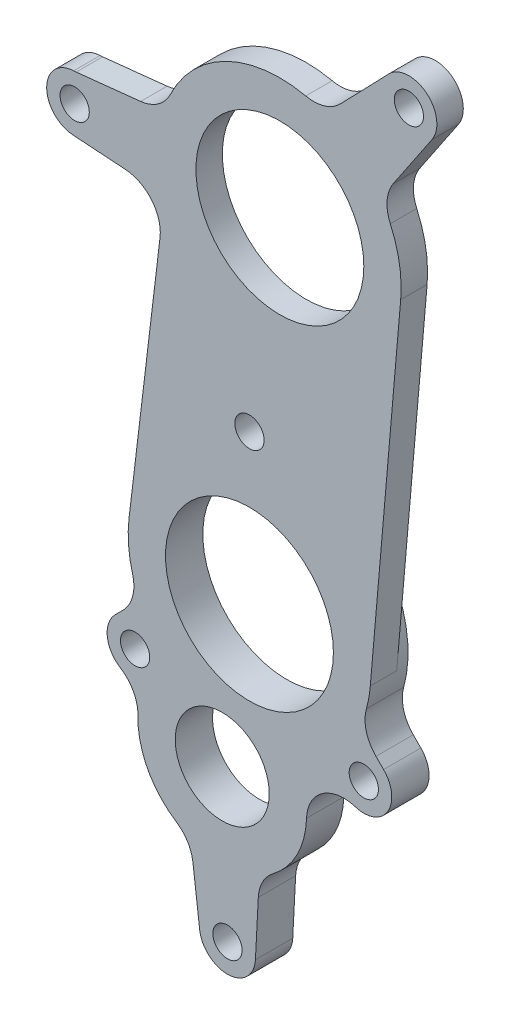
SolidWorks part; units mm, degrees
material "6061-T6 (SS)"
ref_plane "Front Plane" through (0, 0, 0) normal (0, 0, 1) x (1, 0, 0)
ref_plane "Top Plane" through (0, 0, 0) normal (0, 1, 0) x (1, 0, 0)
ref_plane "Right Plane" through (0, 0, 0) normal (1, 0, 0) x (0, 0, -1)
sketch "Sketch1" plane through (0, 0, 0) normal (0, 0, 1) x (1, 0, 0)
  line L0 (0, 0) -> (0, 25.4) construction
  line L1 (0, 0) -> (19.4575, -16.3268) construction
  line L2 (0, 0) -> (-19.4575, -16.3268) construction
  line L3 (-4.7444, 25.8151) -> (-5.2569, 19.9567)
  line L4 (4.7444, 25.8151) -> (5.2569, 19.9567)
  line L5 (22.8251, -12.9592) -> (18.6668, -8.8009)
  line L6 (16.7259, -20.228) -> (11.9087, -16.855)
  line L7 (-16.7259, -20.228) -> (-11.9087, -16.855)
  line L8 (-18.6668, -8.8009) -> (-22.8251, -12.9592)
  circle A0 centre (19.4575, -16.3268) radius 4.7625
  circle A1 centre (0, 25.4) radius 4.7625
  circle A2 centre (-19.4575, -16.3268) radius 4.7625
  circle A3 centre (19.4575, -16.3268) radius 2.4892
  circle A4 centre (-19.4575, -16.3268) radius 2.4892
  circle A5 centre (0, 25.4) radius 2.4892
  circle A6 centre (0, 0) radius 14.2875
  circle A7 centre (0, 0) radius 20.6375
  dimension "D1" = 9.525
  dimension "D4" = 4.9784
  dimension "D13" = 6.35
  dimension "D14" = 28.575
  dimension "D2" = 25.4
  dimension "D5" = 130
  dimension "D6" = 130
  dimension "D7" = 5
  dimension "D8" = 5
  dimension "D9" = 5
  dimension "D10" = 5
  dimension "D11" = 5
  dimension "D12" = 5
extrude "Boss-Extrude1" add sketch "Sketch1" along normal mid plane 6.35 contours A7 A6 | A7 L4 A1 L3 | A7 L6 A0 L5 | A7 L8 A2 L7 | A2 A4 | A1 A5 | A0 A3 | A7 A2 L7 | A7 L6 A0 | A7 A1 L3 region at (-3.9194, 21.5843, 0) region at (0, 30.0278, 0) region at (-2.5754, 19.8877, 0) region at (3.9194, 21.5843, 0) region at (-19.0539, -10.8717, 0) region at (-19.2557, -11.7034, 0) region at (-14.0152, -16.8766, 0) region at (19.0539, -10.8717, 0) region at (14.0152, -16.8766, 0) region at (23.7331, -14.5558, 0)
sketch "Sketch48" plane through (0, 0, 0) normal (0, 0, 1) x (1, 0, 0)
  line L0 (0, 0) -> (-4.6323, -26.2646) construction
  line L1 (1.0144, -51.8975) -> (1.6802, -39.1516)
  line L2 (-8.4685, -52.2302) -> (-10.0261, -39.5624)
  line L3 (-4.6323, -26.2646) -> (-3.7416, -51.649) construction
  line L4 (16.7259, -20.228) -> (11.9087, -16.855) construction
  line L5 (16.7259, -20.228) -> (11.9087, -16.855)
  line L6 (0, 0) -> (5.1756, 59.5213) construction
  line L7 (5.1756, 59.5213) -> (-4.6323, -26.2646) construction
  line L8 (5.1756, 59.5213) -> (0, 25.4) construction
  line L9 (-3.7867, 40.9314) -> (-4.7444, 25.8151)
  line L10 (7.9577, 39.0722) -> (4.7444, 25.8151)
  line L13 (5.1756, 59.5213) -> (-29.7435, 58.8797) construction
  line L14 (5.1756, 59.5213) -> (27.1297, 86.6833) construction
  line L15 (23.7008, 89.9884) -> (12.8133, 78.6934)
  line L16 (31.0804, 84.0238) -> (22.3197, 71.0098)
  line L17 (-30.0714, 54.1285) -> (-14.4206, 53.0485)
  line L18 (-29.7435, 63.6422) -> (-14.6531, 65.2423)
  line L19 (-14.4206, 53.0485) -> (-20.4905, 2.4585)
  line L20 (25.7355, 57.7335) -> (20.5599, -1.7878)
  line L21 (4.7444, 25.8151) -> (5.2569, 19.9567) construction
  line L22 (-4.7444, 25.8151) -> (-5.2569, 19.9567) construction
  line L23 (4.7444, 25.8151) -> (5.2569, 19.9567)
  line L24 (-4.7444, 25.8151) -> (-5.2569, 19.9567)
  circle A0 centre (-4.6323, -26.2646) radius 8
  circle A1 centre (5.1756, 59.5213) radius 14.2875
  circle A2 centre (-4.6323, -26.2646) radius 14.35
  circle A3 centre (0, 25.4) radius 2.4892 construction
  circle A4 centre (-19.4575, -16.3268) radius 2.4892 construction
  circle A5 centre (0, 0) radius 14.2875 construction
  arc A6 (-11.9087, -16.855) -> (11.9087, -16.855) centre (0, 0) ccw construction
  circle A7 centre (-19.4575, -16.3268) radius 2.4892
  circle A8 centre (0, 0) radius 14.2875
  arc A9 (-11.9087, -16.855) -> (11.9087, -16.855) centre (0, 0) ccw
  circle A10 centre (-3.7416, -51.649) radius 4.7625
  circle A11 centre (-3.7416, -51.649) radius 2.4892
  arc A12 (-22.8251, -12.9592) -> (-16.7259, -20.228) centre (-19.4575, -16.3268) ccw construction
  circle A13 centre (19.4575, -16.3268) radius 2.4892 construction
  arc A14 (9.7108, -26.7096) -> (18.0005, -20.8609) centre (16.0577, -26.9065) cw
  circle A15 centre (19.4575, -16.3268) radius 4.7625 construction
  circle A16 centre (19.4575, -16.3268) radius 4.7625
  circle A17 centre (5.1756, 59.5213) radius 20.6375
  arc A18 (18.6668, -8.8009) -> (5.2569, 19.9567) centre (0, 0) ccw construction
  arc A19 (4.7444, 25.8151) -> (-4.7444, 25.8151) centre (0, 25.4) ccw construction
  circle A20 centre (-29.7435, 58.8797) radius 2.4892
  circle A21 centre (-29.7435, 58.8797) radius 4.7625
  circle A22 centre (27.1297, 86.6833) radius 2.4892
  circle A23 centre (27.1297, 86.6833) radius 4.7625
  arc A24 (4.7444, 25.8151) -> (-4.7444, 25.8151) centre (0, 25.4) ccw
  arc A25 (-5.2569, 19.9567) -> (-18.6668, -8.8009) centre (0, 0) ccw construction
  arc A26 (-5.2569, 19.9567) -> (-18.6668, -8.8009) centre (0, 0) ccw
  arc A27 (18.6668, -8.8009) -> (5.2569, 19.9567) centre (0, 0) ccw
  circle A28 centre (0, 0) radius 20.6375 construction
  circle A29 centre (0, 0) radius 20.6375
  dimension "D3" = 16
  dimension "D9" = 6.35
  dimension "D1" = 26.67
  dimension "D2" = 51.8719
  dimension "D5" = 77.1398
  dimension "D6" = 5
  dimension "D7" = 5
  dimension "D8" = 25.4
  dimension "D10" = 59.7459
  dimension "D11" = 86.3448
  dimension "D12" = 5
  dimension "D13" = 5
  dimension "D14" = 34.925
  dimension "D15" = 80.322
  dimension "D16" = 130
  dimension "D17" = 5
  dimension "D18" = 5
  dimension "D19" = 5
  dimension "D20" = 5
  dimension "D4" = 6.35
extrude "Boss-Extrude2" add sketch "Sketch48" along normal mid plane 6.35 contours L0 A8 A2 A7 A9 A0 | A10 L1 A2 L2 | A10 A11 | A16 L5 A9 A2 A14 | A17 A1 | A23 L15 A17 L16 | A23 A22 | A21 L17 A17 L18 | A21 A20 | A24 L10 A17 L9 | A26 L24 L9 A17 L19 | A27 L20 A17 L10 L23 region at (-4.006, -44.1148, 0) region at (-3.5793, -56.274, 0) region at (-4.1425, -40.2232, 0) region at (11.573, -20.226, 0) region at (-11.6918, 30.1563, 0) region at (-20.5371, 59.0307, 0) region at (-14.8746, 59.139, 0) region at (-34.3686, 59.0391, 0) region at (1.1901, 34.3434, 0) region at (15.9999, 28.5001, 0) region at (21.3451, 79.5266, 0) region at (28.8613, 90.9749, 0)
extrude "Cut-Extrude1" cut sketch "Sketch48<3>" against normal through all both and the other way through all contours A0 A9 region at (-3.4288, -19.4409, 0)
sketch "Sketch48<3>" plane through (0, 0, 0) normal (0, 0, 1) x (1, 0, 0) same geometry as "Sketch48"
sketch "Sketch49" plane through (0, 0, -3.175) normal (0, 0, -1) x (-1, 0, 0)
  circle A0 centre (-5.1756, 59.5213) radius 17.8597
extrude "Cut-Extrude4" cut sketch "Sketch48<5>" along normal blind 1.8517 from surface contours A24 L10 A17 L9 | A26 L24 L9 A17 L19 | A17 A1 | A21 L17 A17 L18 | A21 A20 | A23 L15 A17 L16 | A23 A22 | A27 L20 A17 L10 L23 | A29 L23 A24 L24 region at (-11.6918, 30.1563, 0) region at (-20.5371, 59.0307, 0) region at (-14.8746, 59.139, 0) region at (0, 24.7649, 0) region at (-34.3686, 59.0391, 0) region at (1.1901, 34.3434, 0) region at (15.9999, 28.5001, 0) region at (21.3451, 79.5266, 0) region at (28.8613, 90.9749, 0) starting at face at (0.5978, 14.7383, -3.175)
sketch "Sketch48<5>" plane through (0, 0, 0) normal (0, 0, 1) x (1, 0, 0) same geometry as "Sketch48"
fillet "Fillet1" radius 6.35 10 edges at (-14.4206, 53.0485, 0.9258) (-29.7435, 63.6422, 0.9258) (-14.6531, 65.2423, 0.9258) (12.8133, 78.6934, 0.9258) (18.6668, -8.8009, 0) (1.6802, -39.1516, 0) (-10.0261, -39.5624, 0) (-17.9144, -20.8324, 0) (-18.6668, -8.8009, 0) (22.3197, 71.0098, 0.9258)
equation "\"D7@Sketch48\"=\"D6@Sketch48\""
equation "\"D3@Sketch48\"=16mm"
equation "\"D18@Sketch48\"=\"D17@Sketch48\""
equation "\"D19@Sketch48\"=\"D17@Sketch48\""
